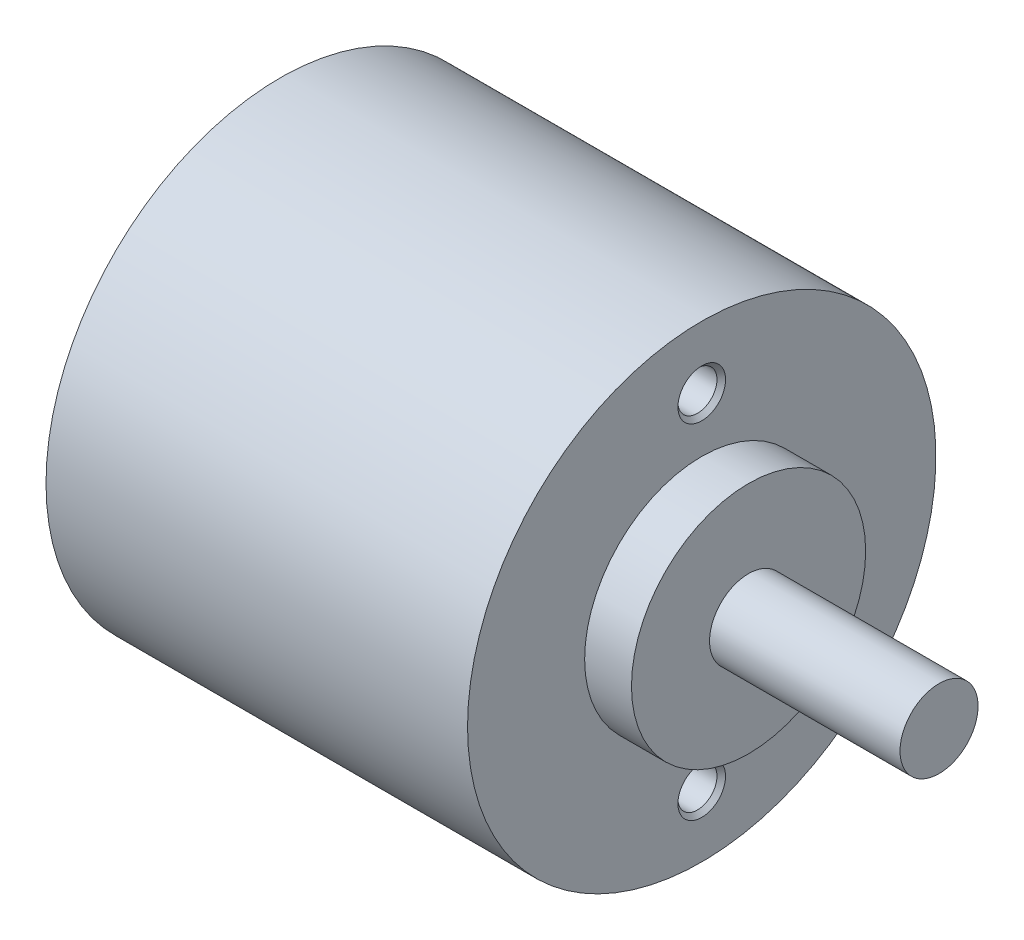
SolidWorks part; units mm, degrees
ref_plane "Plan de face" through (0, 0, 0) normal (0, 0, 1) x (1, 0, 0)
ref_plane "Plan de dessus" through (0, 0, 0) normal (0, 1, 0) x (1, 0, 0)
ref_plane "Plan de droite" through (0, 0, 0) normal (1, 0, 0) x (0, 0, -1)
sketch "Esquisse1" plane through (0, 0, 0) normal (0, 0, 1) x (1, 0, 0)
  line L0 (-51.1551, 0) -> (25.063, 0) construction
  line L1 (15.2, 2.5) -> (15.2, 0)
  line L2 (15.2, 0) -> (-27, 0)
  line L3 (-27, 0) -> (-27, 15)
  line L4 (-27, 15) -> (0, 15)
  line L5 (0, 15) -> (0, 7.5)
  line L6 (3, 2.5) -> (15.2, 2.5)
  line L7 (0, 7.5) -> (3, 7.5)
  line L8 (3, 7.5) -> (3, 2.5)
  dimension "D1" = 30
  dimension "D2" = 5
  dimension "D3" = 15.2
  dimension "D4" = 27
  dimension "D5" = 3
  dimension "D6" = 15
revolve "Révolution1" add sketch "Esquisse1" angle 360 about L0
hole_wizard "Trou taraudé M3x0.51" positions "Esquisse4" profile "Esquisse3" tap size "M3x0.5" standard "Ansi Metric"
sketch "Esquisse4" plane through (0, 0, 0) normal (1, 0, 0) x (0, 0, -1)
  circle A0 centre (0, 0) radius 11 construction
  point P0 (0, 11)
  point P2 (0, -11)
  dimension "D1" = 22
sketch "Esquisse3" plane through (0, 11, 0) normal (0, 1, 0) x (0, 0, -1)
  line L0 (0, 0) -> (0, 9.2511)
  line L1 (0, 9.2511) -> (1.25, 8.5)
  line L2 (1.25, 8.5) -> (1.25, 0.275)
  line L3 (1.25, 0.275) -> (1.525, 0)
  line L5 (1.525, 0) -> (0, 0)
  line L6 (-1.25, 0.275) -> (-1.525, 0) construction
  line L10 (0, 9.2511) -> (-1.25, 8.5) construction
  line L11 (0, -6.35) -> (0, 107.95) construction
  dimension "Diamètre du trou pour taraudage" = 2.5
  dimension "Profondeur du trou pour taraudage" = 8.5
  dimension "Diamètre du fraisage entrant" = 3.05
  dimension "Angle du fraisage entrant" = 90
  dimension "Angle de pointe" = 118
cosmetic thread "Filetage de perçage1" parameters "D1"=6, "D2"=3
cosmetic thread "Filetage de perçage2" parameters "D1"=6, "D2"=3
